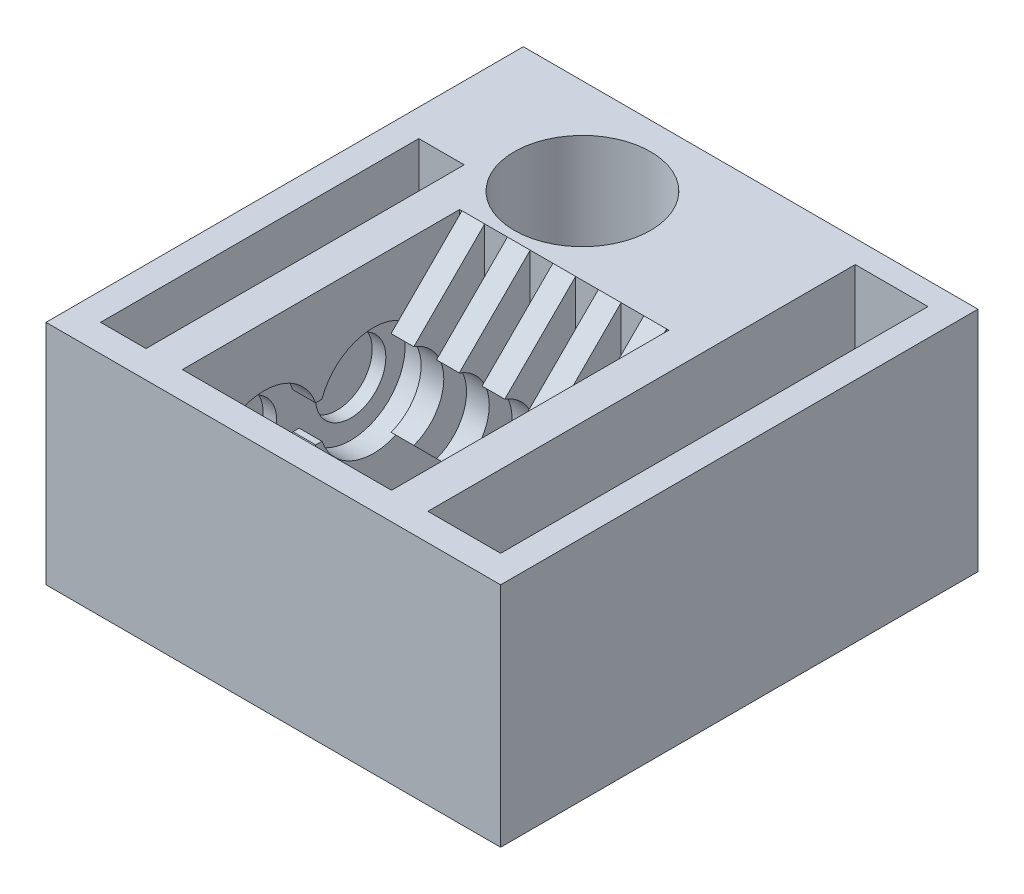
SolidWorks part; units mm, degrees
ref_plane "Front Plane" through (0, 0, 0) normal (0, 0, 1) x (1, 0, 0)
ref_plane "Top Plane" through (0, 0, 0) normal (0, 1, 0) x (1, 0, 0)
ref_plane "Right Plane" through (0, 0, 0) normal (1, 0, 0) x (0, 0, -1)
sketch "Sketch2" plane through (0, 0, 0) normal (0, 1, 0) x (1, 0, 0)
  line L0 (0, 54.9293) -> (0, -74.9036) construction
  line L1 (-50, 52.5) -> (50, 52.5)
  line L2 (-50, 52.5) -> (-50, -52.5)
  line L3 (-50, -52.5) -> (50, -52.5)
  line L4 (50, 52.5) -> (50, -52.5)
  line L5 (-72.7442, 0) -> (103.5154, 0) construction
  dimension "D1" = 105
  dimension "D2" = 100
extrude "Boss-Extrude1" add sketch "Sketch2" along normal blind 50
sketch "Sketch3" plane through (0, 50, 0) normal (0, 1, 0) x (1, 0, 0)
  line L0 (-69.2782, 0) -> (105.7343, 0) construction
  line L1 (0, 63.7563) -> (0, -72.2212) construction
  line L3 (-50, 52.5) -> (-50, -52.5) construction
  line L4 (50, 52.5) -> (-50, 52.5) construction
  circle A0 centre (-39, 0) radius 5 construction
  circle A1 centre (-39, 0) radius 39 construction
  circle A2 centre (-16.0054, 31.5) radius 15
  dimension "D1" = 10
  dimension "D2" = 6
  dimension "D3" = 78
  dimension "D4" = 30
  dimension "D5" = 6
extrude "Cut-Extrude1" cut sketch "Sketch3" against normal up to next
sketch "Sketch5" plane through (0, 50, 0) normal (0, 1, 0) x (1, 0, 0)
  line L0 (50, -52.5) -> (50, 52.5) construction
  line L1 (28, 33.5) -> (44, 33.5)
  line L2 (28, 33.5) -> (28, -46.5)
  line L3 (28, -46.5) -> (44, -46.5)
  line L4 (44, 33.5) -> (44, -46.5)
  line L5 (-44, 23.5) -> (-34, 23.5)
  line L6 (-44, 23.5) -> (-44, -46.5)
  line L7 (-44, -46.5) -> (-34, -46.5)
  line L8 (-34, 23.5) -> (-34, -46.5)
  line L9 (-50, -52.5) -> (50, -52.5) construction
  line L10 (-50, 52.5) -> (-50, -52.5) construction
  dimension "D1" = 6
  dimension "D2" = 6
  dimension "D3" = 80
  dimension "D4" = 16
  dimension "D5" = 6
  dimension "D6" = 6
  dimension "D7" = 70
  dimension "D8" = 10
extrude "Cut-Extrude3" cut sketch "Sketch5" against normal up to next
sketch "Sketch6" plane through (28, 0, 0) normal (1, 0, 0) x (0, 0, -1)
  line L0 (-16.5, 56.9811) -> (-16.5, -19.2113) construction
  line L1 (-69.1636, 25) -> (71.5534, 25) construction
  line L2 (-17.1863, 29) -> (-15.8137, 29)
  line L3 (-17.1863, 21) -> (-15.8137, 21)
  line L4 (-46.5, 0) -> (33.5, 0)
  line L5 (33.5, 0) -> (33.5, 50)
  line L6 (33.5, 50) -> (-46.5, 50)
  line L7 (-46.5, 50) -> (-46.5, 0)
  line L8 (-46.5, 0) -> (33.5, 0) construction
  line L9 (33.5, 0) -> (33.5, 50) construction
  line L10 (33.5, 50) -> (-46.5, 50) construction
  line L11 (-46.5, 50) -> (-46.5, 0) construction
  arc A0 (-17.1863, 29) -> (-17.1863, 21) centre (-28.5, 25) ccw
  circle A2 centre (-28.5, 25) radius 9 construction
  arc A3 (-15.8137, 29) -> (-15.8137, 21) centre (-4.5, 25) cw
  arc A4 (-16.5, 25) -> (-17.1863, 29) centre (-28.5, 25) ccw construction
  arc A5 (-17.1863, 21) -> (-16.5, 25) centre (-28.5, 25) ccw construction
  arc A6 (-15.8137, 21) -> (-16.5, 25) centre (-4.5, 25) cw construction
  arc A7 (-16.5, 25) -> (-15.8137, 29) centre (-4.5, 25) cw construction
  dimension "D4" = 24
  dimension "D5" = 18
  dimension "D2" = 30
  dimension "D3" = 25
  dimension "D6" = 12
  dimension "D7" = 12
  dimension "D8" = 4
  dimension "D1" = 0
extrude "Cut-Extrude4" cut sketch "Sketch6" against normal blind 31
sketch "Sketch7" plane through (28, 0, 0) normal (1, 0, 0) x (0, 0, -1)
  line L0 (-17.1863, 21) -> (-15.8137, 21) construction
  line L1 (-15.8137, 29) -> (-17.1863, 29) construction
  line L2 (-17.1863, 21) -> (-15.8137, 21)
  line L3 (-15.8137, 29) -> (-17.1863, 29)
  arc A6 (-15.8137, 21) -> (-15.8137, 29) centre (-4.5, 25) ccw construction
  arc A7 (-17.1863, 29) -> (-17.1863, 21) centre (-28.5, 25) ccw construction
  arc A8 (-15.8137, 21) -> (-15.8137, 29) centre (-4.5, 25) ccw
  arc A9 (-17.1863, 29) -> (-17.1863, 21) centre (-28.5, 25) ccw
  circle A10 centre (-28.5, 25) radius 7.75
  circle A11 centre (-4.5, 25) radius 7.75
  dimension "D1" = 15.5
  dimension "D2" = 15.5
extrude "Boss-Extrude2" add sketch "Sketch7" against normal blind 3
ref_plane "Plane1" through (-3, 0, 0) normal (1, 0, 0) x (0, 0, -1)
mirror "Mirror1" about plane through (-3, 0, 0) normal (1, 0, 0) of "Boss-Extrude2", "Cut-Extrude4"
sketch "Sketch11" plane through (0, 50, 0) normal (0, 1, 0) x (1, 0, 0)
  line L0 (50, 52.5) -> (-50, 52.5) construction
  line L1 (28, 47.5) -> (44, 47.5)
  line L2 (28, 47.5) -> (28, 33.5)
  line L3 (28, 33.5) -> (44, 33.5)
  line L4 (44, 47.5) -> (44, 33.5)
  line L5 (44, -46.5) -> (44, 33.5) construction
  line L6 (28, 33.5) -> (28, -46.5) construction
  line L7 (44, 33.5) -> (28, 33.5) construction
  dimension "D1" = 5
extrude "Cut-Extrude7" cut sketch "Sketch11" against normal up to next
sketch "Sketch8" plane through (0, 50, 0) normal (0, 1, 0) x (1, 0, 0)
  line L0 (28, 47.5) -> (28, -46.5) construction
  line L1 (-26, 14.5) -> (20, 14.5)
  line L2 (-26, 14.5) -> (-26, -46.5)
  line L3 (-26, -46.5) -> (20, -46.5)
  line L4 (20, 14.5) -> (20, -46.5)
  line L5 (-34, -46.5) -> (-34, 23.5) construction
  line L6 (-50, -52.5) -> (50, -52.5) construction
  circle A0 centre (-16.0054, 31.5) radius 15 construction
  dimension "D4" = 2
  dimension "D1" = 8
  dimension "D2" = 8
  dimension "D3" = 6
extrude "Cut-Extrude5" cut sketch "Sketch8" against normal up to next
sketch "Sketch9" plane through (28, 0, 0) normal (1, 0, 0) x (0, 0, -1)
  line L0 (-15.8137, 29) -> (-17.1863, 29) construction
  line L1 (-17.1863, 21) -> (-15.8137, 21) construction
  line L2 (-28.5, 25) -> (60.6587, 25) construction
  line L3 (-15.8137, 29) -> (-17.1863, 29) construction
  line L4 (19.5, 55.6457) -> (19.5, -7.192) construction
  line L5 (-46.5, 0) -> (47.5, 0)
  line L6 (47.5, 0) -> (47.5, 50)
  line L7 (47.5, 50) -> (-46.5, 50)
  line L12 (-46.5, 50) -> (-46.5, 0)
  line L16 (-46.5, 50) -> (-46.5, 0) construction
  line L17 (-17.1863, 21) -> (-15.8137, 21) construction
  line L18 (52.5, 50) -> (52.5, 0) construction
  line L21 (47.5, 0) -> (47.5, 50) construction
  arc A1 (-17.1863, 29) -> (-17.1863, 21) centre (-28.5, 25) ccw construction
  circle A7 centre (19.5, 25) radius 12 construction
  arc A15 (-15.8137, 21) -> (-15.8137, 29) centre (-4.5, 25) ccw construction
  arc A16 (-17.1863, 29) -> (-17.1863, 21) centre (-28.5, 25) ccw construction
  arc A17 (-15.8137, 21) -> (-15.8137, 29) centre (-4.5, 25) ccw construction
  circle A18 centre (19.5, 25) radius 1.75
  dimension "D2" = 24
  dimension "D3" = 3.5
  dimension "D4" = 33
  dimension "D1" = 0
extrude "Cut-Extrude8" cut sketch "Sketch9" against normal blind 3
sketch "Sketch13" plane through (0, 0, 0) normal (0, -1, 0) x (1, 0, 0)
  line L0 (-62.8638, -19.5) -> (95.3177, -19.5) construction
  line L1 (5, -14.5) -> (25, -14.5)
  line L2 (5, -14.5) -> (5, -33.5)
  line L3 (5, -33.5) -> (25, -33.5)
  line L4 (25, -14.5) -> (25, -33.5)
  line L5 (50, -52.5) -> (-50, -52.5) construction
  line L6 (28, 46.5) -> (28, -47.5) construction
  dimension "D1" = 19
  dimension "D2" = 20
  dimension "D3" = 33
  dimension "D4" = 5
  dimension "D5" = 3
extrude "Cut-Extrude9" cut sketch "Sketch13" against normal blind 30
ref_plane "Plane2" through (19.5, 0, 0) normal (-1, 0, 0) x (0, 0, 1)
sketch "Sketch14" plane through (19.5, 0, 0) normal (-1, 0, 0) x (0, 0, 1)
  line L0 (-14.5, 50) -> (-14.5, 0)
  line L1 (-14.5, 0) -> (1.0969, 15.5969)
  line L2 (-19.4881, 25) -> (76.5209, 25) construction
  line L3 (-14.5, 50) -> (1.0969, 34.4031)
  line L5 (-14.5, 0) -> (46.5, 0)
  line L6 (46.5, 0) -> (46.5, 50)
  line L7 (46.5, 50) -> (-14.5, 50)
  line L8 (-14.5, 50) -> (-14.5, 30)
  line L9 (-14.5, 30) -> (-14.5, 0)
  line L10 (-14.5, 0) -> (46.5, 0) construction
  line L11 (46.5, 0) -> (46.5, 50) construction
  line L12 (46.5, 50) -> (-14.5, 50) construction
  line L13 (-14.5, 50) -> (-14.5, 30) construction
  line L14 (-14.5, 30) -> (-14.5, 0) construction
  circle A0 centre (4.5, 25) radius 7.75 construction
  circle A1 centre (4.5, 25) radius 7.75 construction
  arc A2 (1.0969, 34.4031) -> (1.0969, 15.5969) centre (4.5, 25) ccw
  circle A3 centre (28.5, 25) radius 7.75 construction
  circle A4 centre (28.5, 25) radius 7.75 construction
  circle A5 centre (28.5, 25) radius 10 construction
  arc A6 (14.5, 25) -> (1.0969, 34.4031) centre (4.5, 25) ccw construction
  arc A7 (1.0969, 15.5969) -> (14.5, 25) centre (4.5, 25) ccw construction
  dimension "D2" = 20
  dimension "D3" = 20
  dimension "D4" = 45
  dimension "D1" = 0
extrude "Boss-Extrude4" add sketch "Sketch14" along normal blind 5 separate body
pattern_linear "LPattern10" count 5 spacing 10 along (-1, 0, 0) of "Boss-Extrude4"
sketch "Sketch15" plane through (14.5, 0, 0) normal (-1, 0, 0) x (0, 0, 1)
  line L0 (46.5, 0) -> (46.5, 50) construction
  line L1 (46.5, 0) -> (46.5, 50)
  line L2 (46.5, 0) -> (31.1441, 15.3559)
  line L3 (-55.9413, 25) -> (86.0247, 25) construction
  line L4 (46.5, 50) -> (31.1441, 34.6441)
  circle A0 centre (28.5, 25) radius 7.75 construction
  circle A1 centre (28.5, 25) radius 7.75 construction
  arc A2 (31.1441, 15.3559) -> (31.1441, 34.6441) centre (28.5, 25) ccw
  arc A3 (31.1441, 34.6441) -> (18.5, 25) centre (28.5, 25) ccw construction
  arc A4 (18.5, 25) -> (31.1441, 15.3559) centre (28.5, 25) ccw construction
  dimension "D1" = 20
  dimension "D2" = 45
extrude "Boss-Extrude5" add sketch "Sketch15" along normal blind 5 separate body
pattern_linear "LPattern11" count 4 spacing 10 along (-1, 0, 0) of "Boss-Extrude5"
